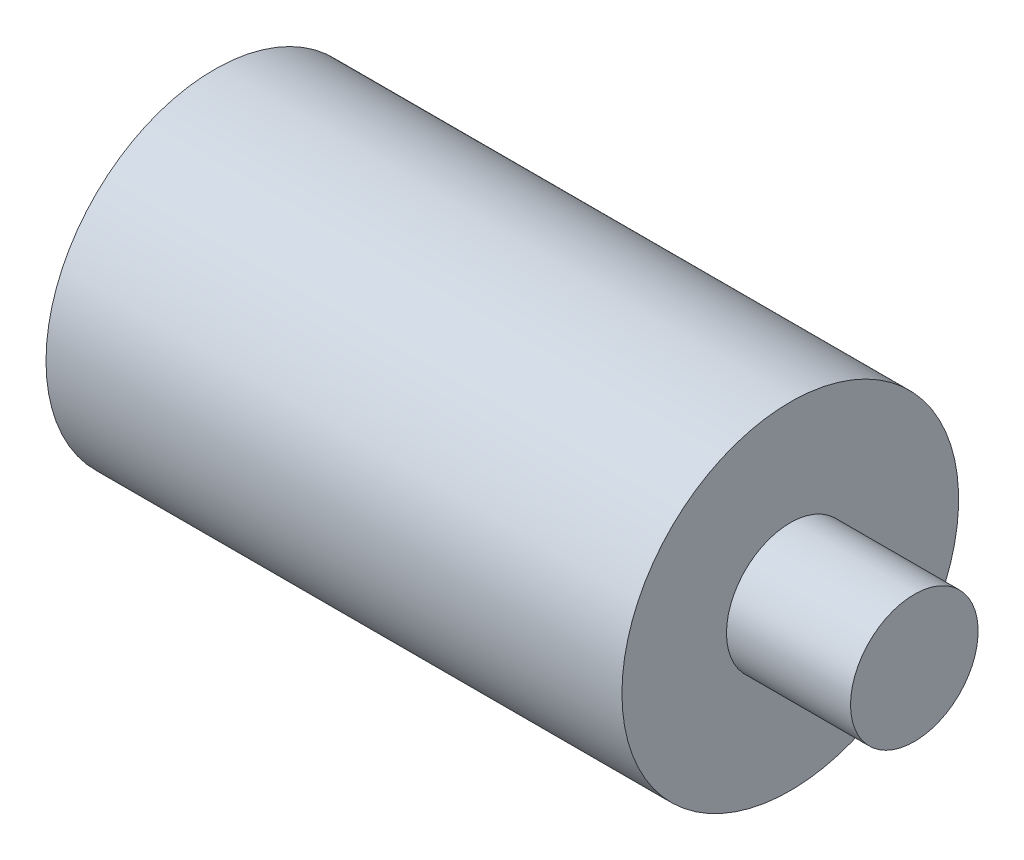
SolidWorks part; units mm, degrees
ref_plane "Front Plane" through (0, 0, 0) normal (0, 0, 1) x (1, 0, 0)
ref_plane "Top Plane" through (0, 0, 0) normal (0, 1, 0) x (1, 0, 0)
ref_plane "Right Plane" through (0, 0, 0) normal (1, 0, 0) x (0, 0, -1)
sketch "Regulator_Ninja Sketch" plane through (0, 0, 0) normal (0, 0, 1) x (1, 0, 0)
  line L0 (-1000, 0) -> (1000, 0) construction
  line L1 (14, 0) -> (14, 7.2)
  line L2 (14, 7.2) -> (0, 7.2)
  line L3 (0, 7.2) -> (0, 19)
  line L4 (0, 19) -> (-65, 19)
  line L5 (-65, 19) -> (-65, 0)
  line L6 (-65, 0) -> (14, 0)
revolve "Regulator_Ninja" add sketch "Regulator_Ninja Sketch" angle 360 about L0
ref_axis "Engine Axis" through (17.95, 0, 0) along (-1, 0, 0)
sketch "Outlet Socket Sketch" plane through (0, 0, 0) normal (0, 0, 1) x (1, 0, 0)
  line L0 (-1000, 0) -> (1000, 0) construction
  line L1 (-66, 0) -> (-51, 0)
  line L2 (-51, 0) -> (-51, 10)
  line L3 (-51, 10) -> (-66, 10)
  line L4 (-66, 10) -> (-66, 0)
revolve "Outlet Socket" cut sketch "Outlet Socket Sketch" angle 360 about L0
